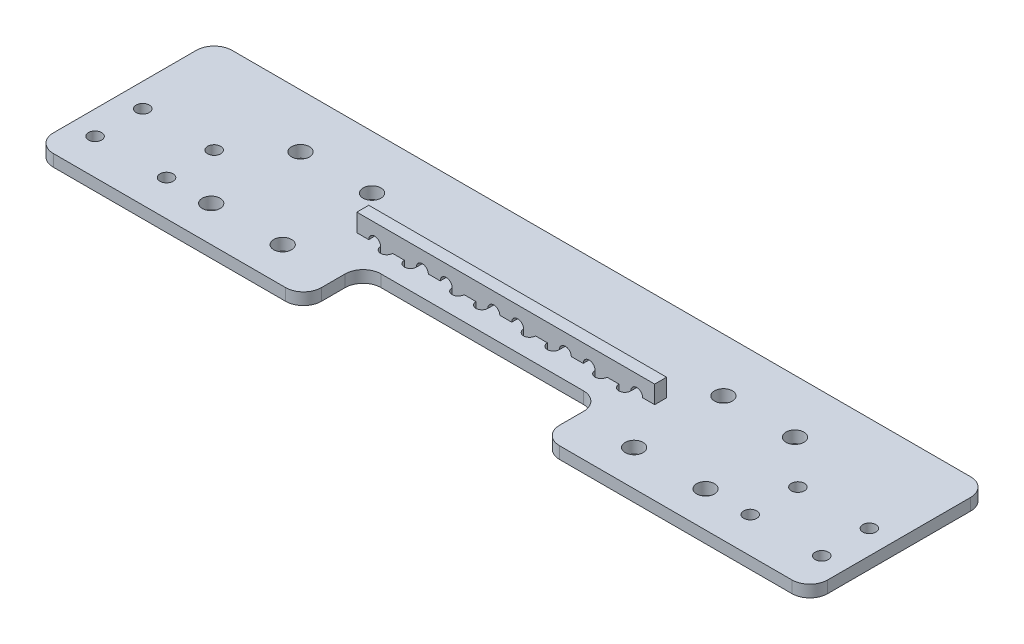
SolidWorks part; units mm, degrees
material "碳管"
ref_plane "前视基准面" through (0, 0, 0) normal (0, 0, 1) x (1, 0, 0)
ref_plane "上视基准面" through (0, 0, 0) normal (0, 1, 0) x (1, 0, 0)
ref_plane "右视基准面" through (0, 0, 0) normal (1, 0, 0) x (0, 0, -1)
sketch "草图1" plane through (0, 0, 0) normal (0, 1, 0) x (1, 0, 0)
  line L0 (65, 30) -> (65, 0) construction
  line L1 (0, 0) -> (130, 0)
  line L2 (0, 0) -> (0, 30)
  line L3 (0, 30) -> (130, 30)
  line L4 (130, 0) -> (130, 30)
  line L5 (0, 15) -> (130, 15) construction
  line L6 (4, 14) -> (4, 6) construction
  line L7 (4, 14) -> (16, 14) construction
  line L8 (16, 14) -> (16, 6) construction
  line L9 (16, 6) -> (4, 6) construction
  circle A0 centre (4, 14) radius 1.1
  circle A1 centre (4, 6) radius 1.1
  circle A2 centre (16, 14) radius 1.1
  circle A3 centre (16, 6) radius 1.1
  circle A4 centre (114, 6) radius 1.1
  circle A5 centre (114, 14) radius 1.1
  circle A6 centre (126, 14) radius 1.1
  circle A7 centre (126, 6) radius 1.1
  dimension "D3" = 2.2
  dimension "D4" = 12
  dimension "D6" = 24
  dimension "D7" = 98
  dimension "D1" = 130
  dimension "D2" = 30
  dimension "D5" = 8
extrude "凸台-拉伸1" add sketch "草图1" along normal blind 2
sketch "草图2" plane through (0, 2, 0) normal (0, 1, 0) x (1, 0, 0)
  line L0 (65, 30) -> (65, 0) construction
  line L1 (130, 30) -> (0, 30) construction
  line L2 (0, 0) -> (130, 0) construction
  line L3 (130, 0) -> (130, 30) construction
  line L4 (45, 0) -> (85, 0)
  line L5 (45, 0) -> (45, 10)
  line L6 (45, 10) -> (85, 10)
  line L7 (85, 0) -> (85, 10)
  line L8 (41, 6.05) -> (38.9, 6.05) construction
  line L9 (38.9, 5) -> (41, 5) construction
  line L10 (38.9, 5) -> (38.9, 11) construction
  line L11 (38.9, 11) -> (41, 11) construction
  line L12 (41, 5) -> (41, 11) construction
  line L13 (38.9, 9.95) -> (41, 9.95) construction
  line L14 (38.9, 8.9) -> (38.9, 7.1) construction
  line L15 (41, 8.9) -> (41, 7.1) construction
  line L16 (41, 22.9) -> (41, 21.1) construction
  line L17 (38.9, 19) -> (41, 19) construction
  line L18 (38.9, 22.9) -> (38.9, 21.1) construction
  line L19 (38.9, 25) -> (41, 25) construction
  line L20 (91.1, 11) -> (89, 11) construction
  line L21 (91.1, 8.9) -> (91.1, 7.1) construction
  line L22 (91.1, 5) -> (89, 5) construction
  line L23 (89, 8.9) -> (89, 7.1) construction
  line L24 (91.1, 25) -> (89, 25) construction
  line L25 (91.1, 22.9) -> (91.1, 21.1) construction
  line L26 (91.1, 19) -> (89, 19) construction
  line L27 (89, 22.9) -> (89, 21.1) construction
  circle A0 centre (110, 30) radius 1 construction
  circle A1 centre (98, 30) radius 1 construction
  circle A2 centre (76, 30) radius 1 construction
  circle A3 centre (88, 30) radius 1 construction
  circle A4 centre (20, 30) radius 1 construction
  circle A5 centre (32, 30) radius 1 construction
  circle A6 centre (42, 30) radius 1 construction
  circle A7 centre (54, 30) radius 1 construction
  arc A8 (38.9, 11) -> (38.9, 8.9) centre (38.9, 9.95) ccw construction
  arc A9 (41, 8.9) -> (41, 11) centre (41, 9.95) ccw construction
  arc A10 (38.9, 7.1) -> (38.9, 5) centre (38.9, 6.05) ccw construction
  arc A11 (41, 5) -> (41, 7.1) centre (41, 6.05) ccw construction
  arc A12 (41, 19) -> (41, 21.1) centre (41, 20.05) ccw construction
  arc A13 (38.9, 21.1) -> (38.9, 19) centre (38.9, 20.05) ccw construction
  arc A14 (38.9, 25) -> (38.9, 22.9) centre (38.9, 23.95) ccw construction
  arc A15 (41, 22.9) -> (41, 25) centre (41, 23.95) ccw construction
  arc A16 (89, 8.9) -> (89, 11) centre (89, 9.95) cw construction
  arc A17 (91.1, 11) -> (91.1, 8.9) centre (91.1, 9.95) cw construction
  arc A18 (91.1, 7.1) -> (91.1, 5) centre (91.1, 6.05) cw construction
  arc A19 (89, 5) -> (89, 7.1) centre (89, 6.05) cw construction
  arc A20 (89, 22.9) -> (89, 25) centre (89, 23.95) cw construction
  arc A21 (91.1, 25) -> (91.1, 22.9) centre (91.1, 23.95) cw construction
  arc A22 (91.1, 21.1) -> (91.1, 19) centre (91.1, 20.05) cw construction
  arc A23 (89, 19) -> (89, 21.1) centre (89, 20.05) cw construction
  dimension "D4" = 2
  dimension "D5" = 20
  dimension "D6" = 12
  dimension "D8" = 10
  dimension "D11" = 5
  dimension "D1" = 20
  dimension "D2" = 10
  dimension "D3" = 40
  dimension "D9" = 2.1
  dimension "D10" = 6
  dimension "D13" = 8
  dimension "D14" = 4
  dimension "D7" = 2
  dimension "D12" = 2
extrude "切除-拉伸1" cut sketch "草图2" against normal through all
fillet "圆角1" radius 3 8 edges at (85, 1, 0) (130, 1, 0) (130, 1, -30) (85, 1, -10) (45, 1, -10) (45, 1, 0) (0, 1, 0) (0, 1, -30)
sketch "草图4" plane through (0, 2, 0) normal (0, 1, 0) x (1, 0, 0)
  line L0 (127, 30) -> (3, 30) construction
  line L1 (99, 30) -> (109, 30)
  line L2 (99, 30) -> (99, 36)
  line L3 (99, 36) -> (109, 36)
  line L4 (109, 30) -> (109, 36)
  line L5 (130, 3) -> (130, 27) construction
  line L6 (65, 30) -> (65, 10) construction
  line L7 (82, 10) -> (48, 10) construction
  line L8 (77, 30) -> (77, 36)
  line L9 (77, 30) -> (87, 30)
  line L10 (87, 30) -> (87, 36)
  line L11 (77, 36) -> (87, 36)
  line L12 (31, 36) -> (21, 36)
  line L13 (21, 30) -> (21, 36)
  line L14 (31, 30) -> (21, 30)
  line L15 (31, 30) -> (31, 36)
  line L16 (53, 30) -> (43, 30)
  line L17 (43, 30) -> (43, 36)
  line L18 (53, 36) -> (43, 36)
  line L19 (53, 30) -> (53, 36)
  dimension "D1" = 10
  dimension "D2" = 6
  dimension "D3" = 21
  dimension "D5" = 12
  dimension "D4" = 2
extrude "凸台-拉伸2" [suppressed] add sketch "草图4" against normal blind 2
fillet "圆角2" [suppressed] radius 1
sketch "草图5" [suppressed] plane through (89, 0, 0) normal (1, 0, 0) x (0, 0, -1)
  line L0 (19, 0) -> (19, 6)
  line L1 (5, 2) -> (5, 0) construction
  line L2 (19, 6) -> (25, 6)
  line L3 (25, 0) -> (19, 0) construction
  line L4 (5, 0) -> (5, -30) construction
  line L6 (30, -5) -> (36, -5)
  line L7 (36, -5) -> (36, -11)
  line L9 (5, 2) -> (5, 0)
  line L16 (11, 0) -> (13, 0) construction
  line L17 (3, 0) -> (0, 0)
  line L19 (5, -30) -> (30, -30)
  line L20 (30, -30) -> (30, -27)
  line L25 (25, 0) -> (25, 6)
  line L26 (13, 0) -> (17, 0)
  line L27 (27, 0) -> (30, 0)
  line L28 (11, 0) -> (11, 6)
  line L29 (11, 6) -> (5, 6)
  line L30 (5, 6) -> (5, 2)
  line L31 (11, 0) -> (5, 0) construction
  line L32 (19, 2) -> (19, 0)
  line L33 (36, -11) -> (30, -11)
  line L34 (30, -3) -> (30, 0)
  line L35 (30, -19) -> (36, -19)
  line L36 (36, -19) -> (36, -25)
  line L37 (36, -25) -> (30, -25)
  line L38 (30, -17) -> (30, -13)
  line L39 (8.3885, -26) -> (27, -26)
  line L41 (27, -26) -> (27, -3)
  line L42 (8.3885, -26) -> (3.9456, 0.6576) construction
  line L43 (27, -3) -> (4, -3)
  line L44 (4, -3) -> (27, -26) construction
  line L45 (8.3885, -26) -> (30, -26) construction
  line L46 (27, -3) -> (4, -26) construction
  line L47 (24.8787, -3) -> (15.5, -12.3787)
  line L48 (27, -5.1213) -> (17.6213, -14.5)
  line L49 (4, -5.1213) -> (13.3787, -14.5)
  line L50 (25.9393, -1.9393) -> (2.9393, -24.9393) construction
  line L51 (4, -3) -> (4, -26)
  line L52 (28.0607, -4.0607) -> (5.0607, -27.0607) construction
  line L53 (6.1213, -3) -> (15.5, -12.3787)
  line L54 (15.5, -16.6213) -> (6.1213, -26)
  line L55 (2.9393, -4.0607) -> (25.9393, -27.0607) construction
  line L56 (0, 0) -> (0, -30)
  line L57 (0, -30) -> (5, -30)
  line L58 (4, -26) -> (8.3885, -26)
  line L59 (5, -30) -> (0, 0) construction
  line L60 (5, -3.0148) -> (4.9845, -3)
  line L61 (5.0607, -1.9393) -> (28.0607, -24.9393) construction
  line L62 (17.6213, -14.5) -> (27, -23.8787)
  line L63 (13.3787, -14.5) -> (4, -23.8787)
  line L64 (15.5, -16.6213) -> (24.8787, -26)
  arc A0 (11, 0) -> (13, 0) centre (12, 0) ccw
  arc A1 (3, 0) -> (5, 0) centre (4, 0) ccw
  arc A2 (17, 0) -> (19, 0) centre (18, 0) ccw
  arc A3 (25, 0) -> (27, 0) centre (26, 0) ccw
  arc A4 (30, -3) -> (30, -5) centre (30, -4) ccw
  arc A5 (30, -11) -> (30, -13) centre (30, -12) ccw
  arc A6 (30, -17) -> (30, -19) centre (30, -18) ccw
  arc A7 (30, -25) -> (30, -27) centre (30, -26) ccw
  point P42 (28.0335, -24.9129)
  point P46 (3.841, -1.9129)
  point P47 (25.8393, -2.0499)
  point P48 (7.0134, -25.0499)
  point P49 (25.9665, -27.0871)
  point P50 (1.7739, -4.0871)
  point P51 (28.1607, -3.9501)
  point P52 (9.3349, -26.9501)
  dimension "D1" = 2
  dimension "D2" = 25
  dimension "D4" = 6
  dimension "D5" = 30
  dimension "D6" = 3
  dimension "D7" = 6
  dimension "D8" = 8
  dimension "D9" = 5
  dimension "D11" = 8
  dimension "D13" = 3
  dimension "D14" = 3
  dimension "D15" = 23
  dimension "D17" = 1.5
  dimension "D12" = 4
  dimension "D16" = 1.5
  dimension "D18" = 1.5
  dimension "D19" = 1.5
  dimension "D3" = 2
  dimension "D10" = 2
extrude "凸台-拉伸3" [suppressed] add sketch "草图5" along normal blind 2 separate body
fillet "圆角3" [suppressed] radius 1
fillet "圆角4" [suppressed] radius 1
ref_plane "基准面1" through (65, 0, 0) normal (-1, 0, 0) x (0, 0, 1)
mirror "镜向1" [suppressed] about plane through (65, 0, 0) normal (-1, 0, 0) of bodies 109
sketch "草图6" plane through (0, 2, 0) normal (0, 1, 0) x (1, 0, 0)
  line L0 (39.95, 19) -> (39.95, 11) construction
  line L1 (127, 30) -> (3, 30) construction
  line L3 (39.95, 15) -> (78.1699, 15) construction
  line L4 (65, 30) -> (65, 2.546) construction
  line L5 (127, 30) -> (3, 30) construction
  line L6 (56, 16.05) -> (56, 13.95)
  line L7 (44, 16.05) -> (50, 16.05)
  line L8 (44, 16.05) -> (44, 13.95)
  line L9 (44, 13.95) -> (50, 13.95)
  line L10 (50, 16.05) -> (50, 13.95)
  line L11 (44, 16.05) -> (50, 13.95) construction
  line L12 (44, 13.95) -> (50, 16.05) construction
  line L13 (56, 16.05) -> (62, 16.05)
  line L14 (62, 16.05) -> (62, 13.95)
  line L15 (56, 13.95) -> (62, 13.95)
  line L16 (68, 16.05) -> (68, 13.95)
  line L17 (68, 16.05) -> (74, 16.05)
  line L18 (74, 16.05) -> (74, 13.95)
  line L19 (68, 13.95) -> (74, 13.95)
  line L20 (80, 16.05) -> (80, 13.95)
  line L21 (80, 16.05) -> (86, 16.05)
  line L22 (86, 16.05) -> (86, 13.95)
  line L23 (80, 13.95) -> (86, 13.95)
  circle A0 centre (45, 16.05) radius 1
  circle A1 centre (45, 13.95) radius 1
  circle A2 centre (49, 16.05) radius 1
  circle A3 centre (49, 13.95) radius 1
  circle A4 centre (57, 16.05) radius 1
  circle A5 centre (61, 16.05) radius 1
  circle A6 centre (61, 13.95) radius 1
  circle A7 centre (57, 13.95) radius 1
  circle A8 centre (69, 16.05) radius 1
  circle A9 centre (73, 16.05) radius 1
  circle A10 centre (73, 13.95) radius 1
  circle A11 centre (69, 13.95) radius 1
  circle A12 centre (81, 16.05) radius 1
  circle A13 centre (85, 16.05) radius 1
  circle A14 centre (85, 13.95) radius 1
  circle A15 centre (81, 13.95) radius 1
  point P4 (0, 0)
  point P12 (47, 15)
  point P25 (0, 0)
  point P26 (0, 0)
  point P63 (0, 0)
  point P68 (68.794, 27.7211)
  point P69 (40.794, 19.7211)
  point P70 (69.206, 19.7211)
  point P71 (41.206, 27.7211)
  point P72 (69.206, 26.2789)
  point P73 (41.206, 18.2789)
  point P74 (68.794, 18.2789)
  point P75 (40.794, 26.2789)
  dimension "D2" = 2
  dimension "D1" = 2.1
  dimension "D3" = 6
  dimension "D5" = 6
  dimension "D6" = 15
  dimension "D4" = 4
extrude "切除-拉伸2" cut sketch "草图6" against normal through all contours A13 | A12 | A15 | A14 | L21 L22 L23 L20 | A9 | A8 | A11 | A10 | L17 L18 L19 L16 | L14 L15 L6 L13 | A5 | A6 | A4 | A7 | L10 L9 L8 L7 | A2 | A0 | A3 | A1
sketch "草图7" plane through (0, 0, -13.95) normal (0, 0, -1) x (-1, 0, 0)
  line L0 (0, 0) -> (-96.0406, 0) construction
  line L1 (-44, 0) -> (-44, 2) construction
  line L2 (-44, 0) -> (-44, 2) construction
  line L3 (-50, 0) -> (-50, 2) construction
  line L4 (-50, 0) -> (-50, 2) construction
  line L5 (-44, 2) -> (-44, -2)
  line L6 (-44, -2) -> (-50, -2)
  line L7 (-50, -2) -> (-50, 2)
  line L8 (-56, 2) -> (-56, -2)
  line L9 (-56, -2) -> (-62, -2)
  line L10 (-62, -2) -> (-62, 2)
  line L11 (-68, 2) -> (-68, -2)
  line L12 (-68, -2) -> (-74, -2)
  line L13 (-74, -2) -> (-74, 2)
  line L14 (-80, 2) -> (-80, -2)
  line L15 (-80, -2) -> (-86, -2)
  line L16 (-86, -2) -> (-86, 2)
  line L17 (-43, 2) -> (-55, 2) construction
  line L18 (-42, 2) -> (-40, 2)
  line L19 (-40, 2) -> (-40, 5)
  line L20 (-40, 5) -> (-90, 5)
  line L21 (-90, 5) -> (-90, 2)
  line L22 (-90, 2) -> (-88, 2)
  line L23 (-52, 2) -> (-54, 2)
  line L24 (-64, 2) -> (-66, 2)
  line L25 (-76, 2) -> (-78, 2)
  circle A0 centre (-43, 2) radius 1
  circle A1 centre (-51, 2) radius 1
  circle A2 centre (-55, 2) radius 1
  circle A3 centre (-63, 2) radius 1
  circle A4 centre (-67, 2) radius 1
  circle A5 centre (-75, 2) radius 1
  circle A6 centre (-79, 2) radius 1
  circle A7 centre (-87, 2) radius 1
  line M8 (-48, 0) -> (-46, 0)
  line M9 (-46, 0) -> (-46, 2)
  line M10 (-46, 2) -> (-48, 2)
  line M11 (-48, 2) -> (-48, 0)
  dimension "D2" = 2
  dimension "D1" = 2
  dimension "D4" = 12
  dimension "D5" = 3
  dimension "D6" = 2
  dimension "D7" = 2
  dimension "D3" = 4
extrude "凸台-拉伸4" add sketch "草图7" along normal blind 2 separate body contours A7 L16 L15 L14 A6 L25 A5 L13 L12 L11 A4 L24 A3 L10 L9 L8 A2 L23 A1 L7 L6 L5 A0 L18 L19 L20 L21 L22 M8 M11 M10 M9 | M11 M8 M9 M10 region at (65.3138, 2.138, -13.95) region at (47, 1, -13.95)
sketch "草图8" plane through (0, 0, 0) normal (0, -1, 0) x (1, 0, 0)
  circle A0 centre (23.5, -6) radius 1.5 construction
  circle A1 centre (23.5, -21) radius 1.5 construction
  circle A2 centre (35.5, -21) radius 1.5 construction
  circle A3 centre (35.5, -6) radius 1.5 construction
  circle A4 centre (94.5, -21) radius 1.5 construction
  circle A5 centre (94.5, -6) radius 1.5 construction
  circle A6 centre (106.5, -6) radius 1.5 construction
  circle A7 centre (106.5, -21) radius 1.5 construction
  circle A8 centre (23.5, -6) radius 1.5
  circle A9 centre (23.5, -21) radius 1.5
  circle A10 centre (35.5, -21) radius 1.5
  circle A11 centre (35.5, -6) radius 1.5
  circle A12 centre (94.5, -21) radius 1.5
  circle A13 centre (94.5, -6) radius 1.5
  circle A14 centre (106.5, -6) radius 1.5
  circle A15 centre (106.5, -21) radius 1.5
extrude "切除-拉伸3" cut sketch "草图8" against normal through all
